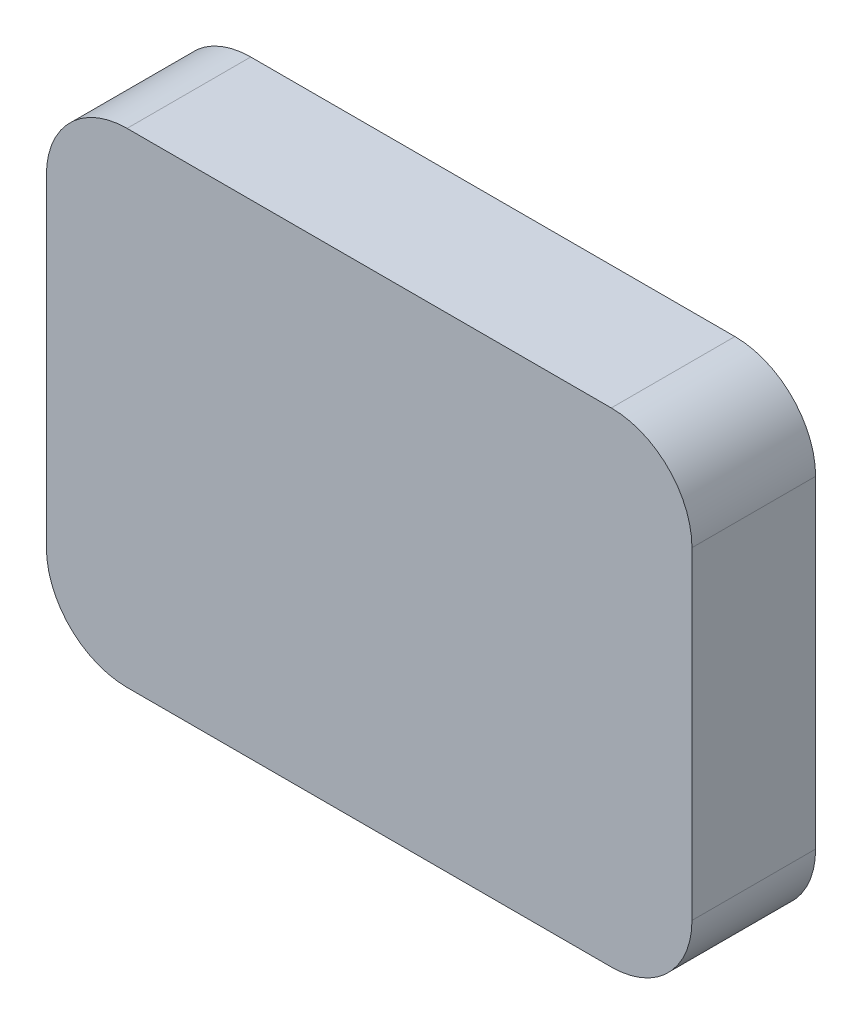
SolidWorks part; units mm, degrees
ref_plane "Plan de face" through (0, 0, 0) normal (0, 0, 1) x (1, 0, 0)
ref_plane "Plan de dessus" through (0, 0, 0) normal (0, 1, 0) x (1, 0, 0)
ref_plane "Plan de droite" through (0, 0, 0) normal (1, 0, 0) x (0, 0, -1)
sketch "Esquisse1" plane through (0, 0, 0) normal (0, 0, 1) x (1, 0, 0)
  line L1 (-30, 30) -> (30, 30)
  line L2 (-40, 20) -> (-40, -20)
  line L3 (-30, -30) -> (30, -30)
  line L4 (40, 20) -> (40, -20)
  line L5 (-40, 30) -> (40, -30) construction
  line L6 (-40, -30) -> (40, 30) construction
  arc A0 (-40, -20) -> (-30, -30) centre (-30, -20) ccw
  arc A1 (30, -30) -> (40, -20) centre (30, -20) ccw
  arc A2 (30, 30) -> (40, 20) centre (30, 20) cw
  arc A3 (-30, 30) -> (-40, 20) centre (-30, 20) ccw
  point P0 (0, 0)
  dimension "D1" = 10
  dimension "D2" = 60
  dimension "D3" = 40
sketch "profil" plane through (0, 0, 0) normal (1, 0, 0) x (0, 0, -1)
  line L0 (0, -27.9) -> (4.1391, -27.9)
  line L1 (4.1391, -27.9) -> (14.1228, -23.8)
  line L3 (14.1228, -30) -> (0, -30)
  line L4 (0, -30) -> (0, -27.9)
  line L6 (0, -20) -> (0, -30) construction
  line L7 (0, -30) -> (0, 30) construction
  line L8 (14.1228, -23.8) -> (14.1228, -25.9)
  line L9 (14.1228, -27.9) -> (14.1228, -30)
  line L10 (14.1228, -23.8) -> (14.1228, -30) construction
  arc A1 (14.1228, -25.9) -> (14.1228, -27.9) centre (14.1228, -26.9) cw
  point P0 (0, 0)
  dimension "D1" = 2
  dimension "D3" = 14.1228
  dimension "D4" = 6.2
sweep "Balayage1" add profiles "profil" path "Esquisse1"
extrude "Boss.-Extru.1" add sketch "Esquisse1<3>" along normal blind 1.2
sketch "Esquisse1<3>" plane through (0, 0, 0) normal (0, 0, 1) x (1, 0, 0) same geometry as "Esquisse1"
fillet "Congé1" radius 2 9 edges at (-35.5861, 25.5861, 0) (-37.9, 0, 0) (-35.5861, -25.5861, 0) (-15, -27.9, 0) (15, -27.9, 0) (35.5861, -25.5861, 0) (37.9, 0, 0) (35.5861, 25.5861, 0) (0, 27.9, 0)
equation "\"buse\"=0.4"
equation "\"coque\"= \"buse\" * 4"
equation "\"diam_silicone\"=2"
equation "\"D1@profil\" = \"diam_silicone\""
equation "\"couche\"=0.2"
equation "\"D1@Boss.-Extru.1\"=\"fond\""
equation "\"fond\"= \"couche\" * 6"
equation "\"D2@Esquisse1\"=\"dim_ext_L@boitier_balaye-1.Part\""
equation "\"D3@profil\"=\"hauteur_boitier@boitier_balaye-1.Part\""
equation "\"D4@profil\"=\"epaisseur_jonction@boitier_balaye-1.Part\""
